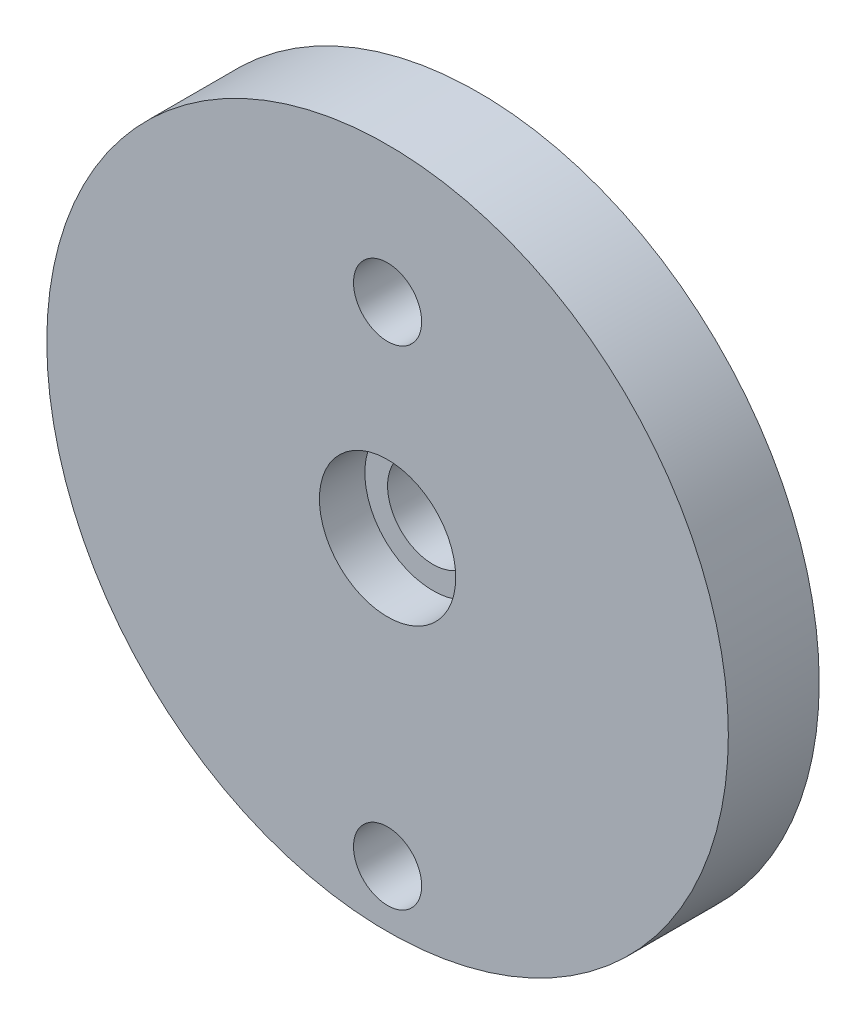
SolidWorks part; units mm, degrees
ref_plane "Front Plane" through (0, 0, 0) normal (0, 0, 1) x (1, 0, 0)
ref_plane "Top Plane" through (0, 0, 0) normal (0, 1, 0) x (1, 0, 0)
ref_plane "Right Plane" through (0, 0, 0) normal (1, 0, 0) x (0, 0, -1)
sketch "Sketch1" plane through (0, 0, 0) normal (0, 0, 1) x (1, 0, 0)
  line L0 (0, -3) -> (0, -12.5) construction
  line L1 (0, 9) -> (0, 15) construction
  circle A0 centre (0, 0) radius 15
  circle A1 centre (0, 0) radius 3
  circle A2 centre (0, -12.5) radius 1.5
  circle A3 centre (0, 9) radius 1.5
  circle A4 centre (0, 0) radius 2
  dimension "D1" = 30
  dimension "D2" = 6
  dimension "D3" = 3
  dimension "D6" = 3
  dimension "D8" = 4
  dimension "D4" = 9.5
  dimension "D5" = 9
  dimension "D7" = 21.5
extrude "Boss-Extrude1" add sketch "Sketch1" along normal blind 4 contours A0 A1 A2 A3 region at (-14.5757, 0, 0)
extrude "Boss-Extrude2" add sketch "Sketch1<3>" along normal blind 2 contours A1 A4 region at (-2.9151, 0, 0)
sketch "Sketch1<3>" plane through (0, 0, 0) normal (0, 0, 1) x (1, 0, 0) same geometry as "Sketch1"
